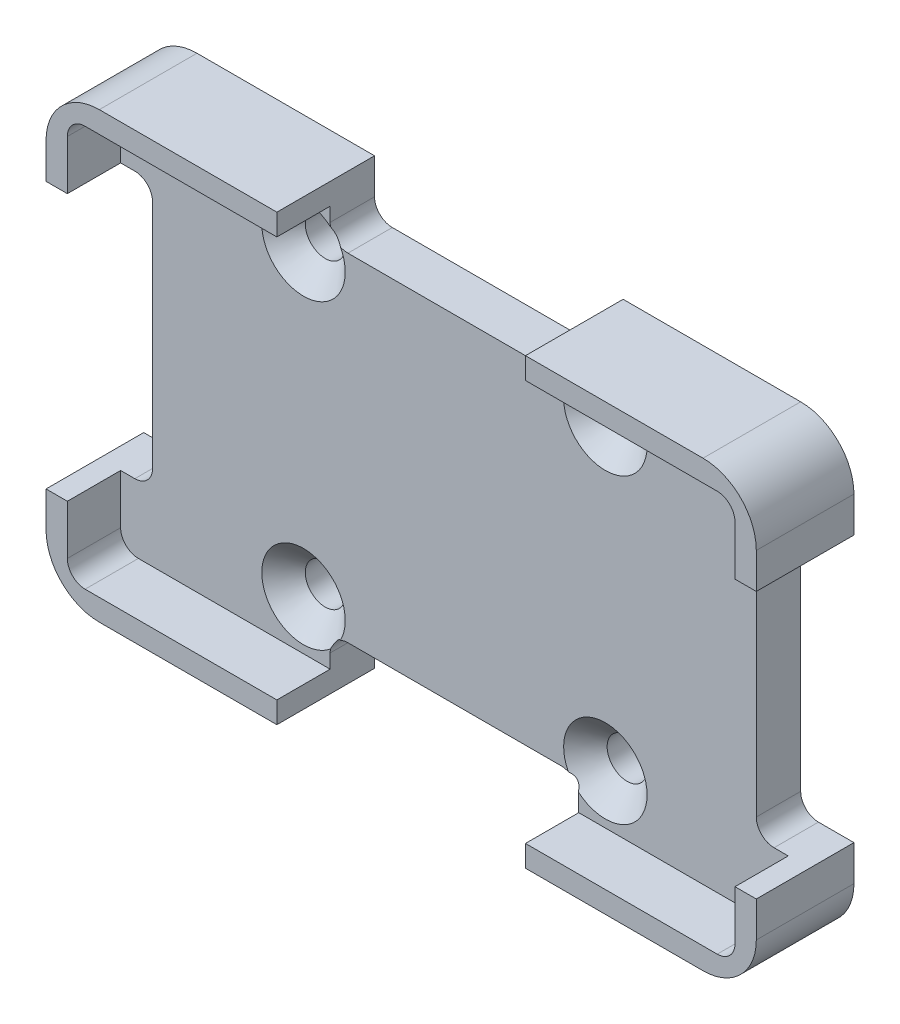
SolidWorks part; units mm, degrees
ref_plane "Front" through (0, 0, 0) normal (0, 0, 1) x (1, 0, 0)
ref_plane "Top" through (0, 0, 0) normal (0, 1, 0) x (1, 0, 0)
ref_plane "Right" through (0, 0, 0) normal (1, 0, 0) x (0, 0, -1)
sketch "XOR_Sketch1 (Mesh)_7" plane through (0, 0, 0) normal (0, 0, 1) x (1, 0, 0)
  line L0 (40, 19) -> (40, 15)
  line L1 (34, 15) -> (40, 15)
  line L2 (-14, -25) -> (-34, -25)
  line L3 (34, -25) -> (14, -25)
  line L4 (-40, -19) -> (-40, -15)
  line L5 (-34, 25) -> (-14, 25)
  line L6 (-14, -19) -> (-14, -25)
  line L7 (-40, 15) -> (-40, 19)
  line L8 (14, 19) -> (-14, 19)
  line L9 (14, 25) -> (34, 25)
  line L10 (14, -19) -> (-14, -19)
  line L11 (34, -15) -> (34, 15)
  line L12 (14, -19) -> (14, -25)
  line L13 (-34, -15) -> (-34, 15)
  line L14 (-40, 15) -> (-34, 15)
  line L15 (-34, -15) -> (-40, -15)
  line L16 (40, -15) -> (34, -15)
  line L17 (-14, 25) -> (-14, 19)
  line L18 (40, -15) -> (40, -19)
  line L19 (14, 25) -> (14, 19)
  arc A0 (34, -25) -> (40, -19) centre (34, -19) ccw
  arc A1 (-40, -19) -> (-34, -25) centre (-34, -19) ccw
  arc A2 (-34, 25) -> (-40, 19) centre (-34, 19) ccw
  arc A3 (40, 19) -> (34, 25) centre (34, 19) ccw
  dimension "D1" = 6
  dimension "D4" = 6
  dimension "D5" = 6
  dimension "D11" = 6
  dimension "D2" = 30
  dimension "D3" = 38
  dimension "D6" = 80
  dimension "D7" = 50
  dimension "D8" = 30
  dimension "D9" = 68
  dimension "D10" = 28
extrude "XOR_Extrude1_8" add sketch "XOR_Sketch1 (Mesh)_7" against normal blind 11 separate body
sketch "XOR_Sketch2 (Mesh)_61" plane through (0, 0, 0) normal (0, 1, 0) x (1, 0, 0)
  arc A0 (45.55, 2.6685) -> (-42.5379, 3.1209) centre (0.6895, -156.116) ccw
  dimension "D1" = 165
sketch "XOR_Sketch4 (Mesh)_141" plane through (0, 0, 0) normal (1, 0, 0) x (0, 0, -1)
  arc A0 (8.1599, 12.4719) -> (8.0236, -12.4632) centre (-89.797, 0.5397) cw
  arc A1 (3.1124, 25.6356) -> (8.1599, 12.4719) centre (-20.6957, 8.957) cw
  arc A2 (0.8347, -24.3644) -> (8.0236, -12.4632) centre (-9.2158, -10.1717) ccw
  point P7 (8.8825, 0)
ref_plane "XOR_Plane1_230" through (20, 0, 0) normal (1, 0, 0) x (0, 0, -1)
sketch "XOR_Sketch5 (Mesh)_231" plane through (20, 0, 0) normal (1, 0, 0) x (0, 0, -1)
  arc A0 (7.081, 12.898) -> (0.4077, 25.1001) centre (-10.6226, 11.1419) ccw
  arc A1 (7.2045, -12.9038) -> (1.202, -24.8999) centre (-11.0501, -11.2694) cw
  arc A2 (7.081, 12.898) -> (7.2045, -12.9038) centre (-129.5744, -0.6577) cw
  point P7 (7.7501, 0)
ref_plane "XOR_Plane2_233" through (-20, 0, 0) normal (1, 0, 0) x (0, 0, -1)
sketch "XOR_Sketch6 (Mesh)_234" plane through (-20, 0, 0) normal (1, 0, 0) x (0, 0, -1)
  arc A0 (6.9509, 12.8691) -> (1.9098, 25.7972) centre (-18.5457, 10.3741) ccw
  arc A1 (6.9613, -12.8696) -> (0.7587, -24.2028) centre (-9.3938, -11.2825) cw
  arc A2 (6.9509, 12.8691) -> (6.9613, -12.8696) centre (-125.1028, -0.0535) cw
  point P7 (7.5817, 0)
ref_plane "XOR_Plane3_239" through (0, 0, 22) normal (0, 0, 1) x (1, 0, 0)
sketch "XOR_Sketch7 (Mesh)_235" plane through (0, 0, 22) normal (0, 0, 1) x (1, 0, 0)
  line L0 (31.5324, -22.6689) -> (-31.1836, -22.6689)
  line L1 (-37.1836, 13.3261) -> (-37.1836, -16.6689)
  line L2 (37.5324, -16.6689) -> (37.5324, 13.5025)
  arc A0 (-37.1836, -16.6689) -> (-31.1836, -22.6689) centre (-31.1836, -16.6689) ccw
  arc A1 (32.8225, 19.3621) -> (-32.5066, 19.1784) centre (0.5697, -127.1293) ccw
  arc A2 (-37.1836, 13.3261) -> (-32.5066, 19.1784) centre (-31.1836, 13.3261) cw
  arc A3 (37.5324, 13.5025) -> (32.8225, 19.3621) centre (31.5324, 13.5025) ccw
  arc A4 (31.5324, -22.6689) -> (37.5324, -16.6689) centre (31.5324, -16.6689) ccw
  dimension "D1" = 150
  dimension "D2" = 6
  dimension "D3" = 6
  dimension "D4" = 6
  dimension "D5" = 6
sketch "XOR_Sketch8 (Mesh)_243" plane through (0, 0, 0) normal (0, 0, 1) x (1, 0, 0)
  line L0 (-10.4237, 0) -> (16.1194, 0) construction
  line L1 (0, 10.039) -> (0, -9.889) construction
  circle A0 centre (-17, -17) radius 3.5
  circle A1 centre (17, 17) radius 3.5
  circle A2 centre (-17, 17) radius 3.5
  circle A3 centre (17, -17) radius 3.5
  dimension "D1" = 7
  dimension "D2" = 7
  dimension "D3" = 7
  dimension "D4" = 7
  dimension "D5" = 34
  dimension "D6" = 34
  dimension "D7" = 34
  dimension "D8" = 34
  dimension "D9" = 17
  dimension "D10" = 17
  dimension "D11" = 17
  dimension "D12" = 17
sketch "XOR_Sketch9 (Mesh)_245" plane through (0, 0, 0) normal (0, 0, 1) x (1, 0, 0)
  circle A0 centre (17, -17) radius 2
  circle A1 centre (-17, 17) radius 2
  circle A2 centre (17, 17) radius 2
  circle A3 centre (-17, -17) radius 2
  dimension "D1" = 4
  dimension "D2" = 4
  dimension "D3" = 4
  dimension "D6" = 4
  dimension "D4" = 34
  dimension "D5" = 34
  dimension "D7" = 34
  dimension "D8" = 17
  dimension "D9" = 17
  dimension "D10" = 34
  dimension "D11" = 17
  dimension "D12" = 17
sketch "草图1" plane through (0, 0, 0) normal (0, 0, 1) x (1, 0, 0)
  line L1 (-37.6, 22.58) -> (37.6, 22.58)
  line L2 (-37.6, 22.58) -> (-37.6, -22.58)
  line L3 (-37.6, -22.58) -> (37.6, -22.58)
  line L4 (37.6, 22.58) -> (37.6, -22.58)
  dimension "D1" = 75.2
  dimension "D2" = 37.6
  dimension "D3" = 45.16
  dimension "D4" = 22.58
extrude "切除-拉伸4" cut sketch "草图1" against normal blind 6
hole_wizard "打孔尺寸(%根据十字)槽半沉头自攻螺钉的类型1" positions "草图3" profile "草图4" size "ST4.2" standard "GB" slot yes end condition through all
sketch "草图3" plane through (0, 0, -6) normal (0, 0, 1) x (1, 0, 0)
  point P0 (-17, 17)
  dimension "D1" = 17
  dimension "D2" = 17
sketch "草图4" plane through (-17, 17, -6) normal (1, 0, 0) x (0, -1, 0)
  line L0 (0, 0) -> (0, 5)
  line L1 (0, 5) -> (2.25, 5)
  line L2 (2.25, 5) -> (2.25, 2.45)
  line L3 (2.25, 2.45) -> (4.7, 0)
  line L5 (4.7, 0) -> (0, 0)
  line L6 (-2.25, 2.45) -> (-4.7, 0) construction
  line L11 (0, -6.35) -> (0, 107.95) construction
  dimension "通孔孔直径" = 4.5
  dimension "通孔孔深度" = 5
  dimension "近端锥形沉头孔直径" = 9.4
  dimension "近端锥形沉头孔角度" = 90
fillet "圆角3" radius 2 12 edges at (-34, -15, -8.5) (-34, 15, -8.5) (-14, 19, -9.0472) (14, 19, -8.5) (34, 15, -8.5) (34, -15, -8.5) (14, -19, -8.5) (-14, -19, -8.5) (-37.6, -22.58, -3) (37.6, -22.58, -3) (37.6, 22.58, -3) (-37.6, 22.58, -3)
pattern_linear "阵列(线性)1" count 2 spacing 34 along (0, -1, 0) count 2 spacing 34 along (1, 0, 0) of "打孔尺寸(%根据十字)槽半沉头自攻螺钉的类型1"
other "边界-曲面1" [suppressed]
extrude "切除-拉伸1" [suppressed] cut sketch "XOR_Sketch7 (Mesh)_235" against normal up to surface (25.8179 mm away)
fillet "圆角1" [suppressed] radius 2
extrude "切除-拉伸2" [suppressed] cut sketch "XOR_Sketch8 (Mesh)_243" against normal blind 10
fillet "圆角2" [suppressed] radius 2
extrude "切除-拉伸3" [suppressed] cut sketch "XOR_Sketch9 (Mesh)_245" against normal through all
